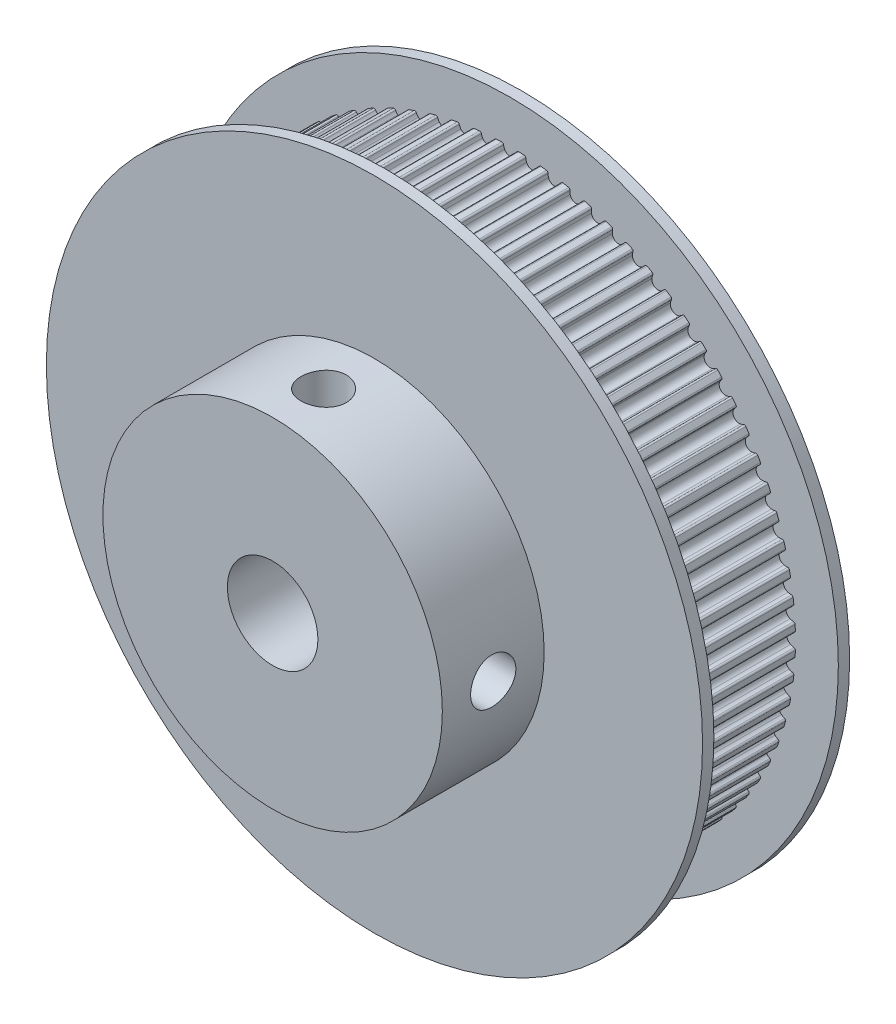
SolidWorks part; units mm, degrees
material "6061 Alloy"
ref_plane "Front Plane" through (0, 0, 0) normal (0, 0, 1) x (1, 0, 0)
ref_plane "Top Plane" through (0, 0, 0) normal (0, 1, 0) x (1, 0, 0)
ref_plane "Right Plane" through (0, 0, 0) normal (1, 0, 0) x (0, 0, -1)
sketch "Sketch1" plane through (0, 0, 0) normal (0, 0, 1) x (1, 0, 0)
  circle A0 centre (0, 0) radius 25.4648 construction
  circle A1 centre (0, 0) radius 25.2108
  dimension "D1" = 50.9296
  dimension "D2" = 0.254
extrude "Boss-Extrude1" add sketch "Sketch1" along normal mid plane 11
sketch "Sketch2" plane through (0, 0, 5.5) normal (0, 0, 1) x (1, 0, 0)
  line L0 (0, 0) -> (0, 25.2108) construction
  line L1 (0, 25.2108) -> (0.4, 25.2108)
  circle A0 centre (0, 0) radius 25.2108 construction
  circle A1 centre (0.4, 25.2108) radius 1 construction
  circle A2 centre (0, 25.0158) radius 0.555 construction
  circle A3 centre (-0.7387, 25.0499) radius 0.15 construction
  circle A4 centre (0, 0) radius 25.2108 construction
  arc A5 (-0.7431, 25.1998) -> (-0.5902, 25.0709) centre (-0.7387, 25.0499) cw
  arc A6 (-0.5902, 25.0709) -> (-0.4989, 24.7726) centre (0.4, 25.2108) ccw
  arc A7 (-0.4989, 24.7726) -> (0.4989, 24.7726) centre (0, 25.0158) ccw
  arc A8 (0.5902, 25.0709) -> (0.4989, 24.7726) centre (-0.4, 25.2108) cw
  arc A9 (0.7431, 25.1998) -> (0.5902, 25.0709) centre (0.7387, 25.0499) ccw
  arc A10 (-0.7431, 25.1998) -> (0.7431, 25.1998) centre (0, 0) cw
  point P23 (0, 25.6998)
  circle M9 centre (0, 0) radius 25.2108
  dimension "D2" = 2
  dimension "D3" = 1.11
  dimension "D5" = 0.3
  dimension "D1" = 0.4
extrude "Cut-Extrude1" cut sketch "Sketch2" against normal through all contours A9 A5 A6 A7 A8 M9 region at (0, 24.8905, 5.5)
pattern_circular "CirPattern1" count 80 over 360 about axis through (0, 0, 5.5) along (0, 0, -1) of "Cut-Extrude1" reverse direction yes
sketch "Sketch3" plane through (0, 0, 5.5) normal (0, 0, 1) x (1, 0, 0)
  circle A0 centre (0, 0) radius 15
  dimension "D1" = 30
extrude "Boss-Extrude2" add sketch "Sketch3" along normal blind 10
sketch "Sketch4" plane through (0, 0, 5.5) normal (0, 0, 1) x (1, 0, 0)
  circle A0 centre (0, 0) radius 29
  dimension "D1" = 58
extrude "Boss-Extrude3" add sketch "Sketch4" along normal blind 1
mirror "Mirror1" about plane through (0, 0, 0) normal (0, 0, 1) of "Boss-Extrude3"
sketch "Sketch5" plane through (0, 0, 15.5) normal (0, 0, 1) x (1, 0, 0)
  circle A0 centre (0, 0) radius 4
  dimension "D1" = 8
extrude "Cut-Extrude2" cut sketch "Sketch5" against normal through all
sketch "Sketch6" plane through (0, 0, 0) normal (1, 0, 0) x (0, 0, -1)
  line L0 (-15.5, 0) -> (-6.5, 0) construction
  line L1 (-15.5, 15) -> (-15.5, -15) construction
  line L2 (-6.5, 15) -> (-6.5, -15) construction
  line L3 (-6.5, 0) -> (21.3245, 6.5161) construction
  circle A0 centre (-11, 0) radius 2
  dimension "D1" = 4
extrude "Cut-Extrude3" cut sketch "Sketch6" along normal through all
pattern_circular "CirPattern2" count 2 over 90 about axis through (0, 0, 15.5) along (0, 0, -1) of "Cut-Extrude3" reverse direction yes
